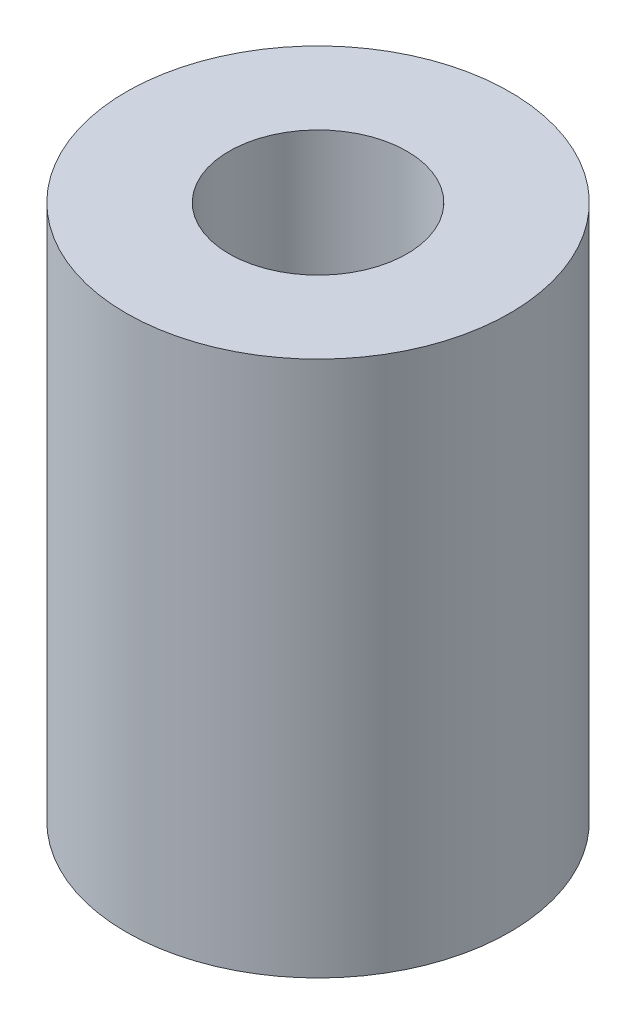
SolidWorks part; units mm, degrees
ref_plane "Front Plane" through (0, 0, 0) normal (0, 0, 1) x (1, 0, 0)
ref_plane "Top Plane" through (0, 0, 0) normal (0, 1, 0) x (1, 0, 0)
ref_plane "Right Plane" through (0, 0, 0) normal (1, 0, 0) x (0, 0, -1)
sketch "Sketch1" plane through (0, 0, 0) normal (0, 1, 0) x (1, 0, 0)
  circle A0 centre (0, 0) radius 3.45
  circle A1 centre (0, 0) radius 1.6
extrude "Boss-Extrude1" add sketch "Sketch1" along normal blind 9.64
